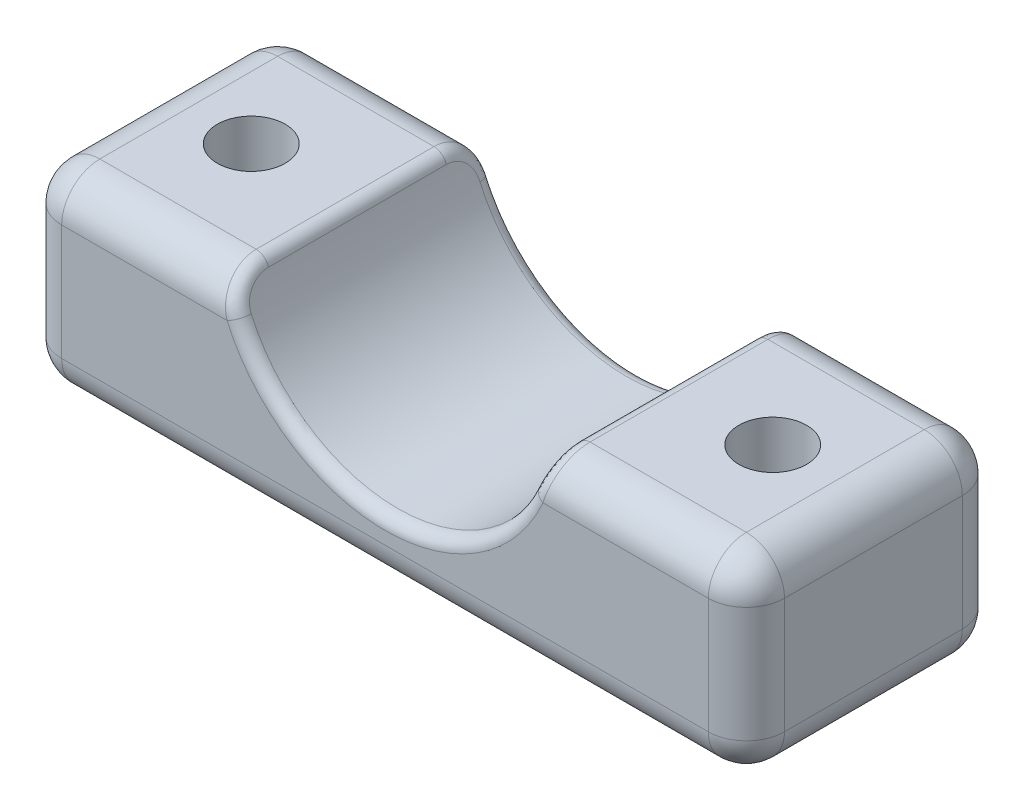
SolidWorks part; units mm, degrees
material "PLA ABS"
ref_plane "Front Plane" through (0, 0, 0) normal (0, 0, 1) x (1, 0, 0)
ref_plane "Top Plane" through (0, 0, 0) normal (0, 1, 0) x (1, 0, 0)
ref_plane "Right Plane" through (0, 0, 0) normal (1, 0, 0) x (0, 0, -1)
sketch "Sketch1" plane through (0, 0, 0) normal (0, 0, 1) x (1, 0, 0)
  line L0 (16.002, 22.352) -> (36.1315, 22.352)
  line L1 (-36.1315, 0) -> (36.1315, 0)
  line L2 (-36.1315, 0) -> (-36.1315, 22.352)
  line L3 (-36.1315, 22.352) -> (-16.002, 22.352)
  line L4 (36.1315, 0) -> (36.1315, 22.352)
  arc A0 (-16.002, 22.352) -> (16.002, 22.352) centre (0, 22.352) ccw
  dimension "D1" = 32.004
  dimension "D2" = 72.263
  dimension "D3" = 6.35
extrude "Boss-Extrude1" add sketch "Sketch1" along normal mid plane 25.4
sketch "Sketch2" plane through (0, 22.352, 0) normal (0, 1, 0) x (1, 0, 0)
  line L0 (-26.0668, 12.7) -> (-26.0667, -12.7) construction
  line L1 (-16.002, 12.7) -> (-36.1315, 12.7) construction
  line L2 (-16.002, -12.7) -> (-36.1315, -12.7) construction
  line L3 (0, 0) -> (0, 12.7) construction
  line L4 (16.002, 12.7) -> (-16.002, 12.7) construction
  circle A0 centre (-26.0668, 0) radius 3.3909
  circle A1 centre (26.0668, 0) radius 3.3909
  dimension "D1" = 6.7818
extrude "Cut-Extrude1" cut sketch "Sketch2" against normal through all
sketch "Sketch3" plane through (0, 0, 12.7) normal (0, 0, 1) x (1, 0, 0)
  line L0 (-16.002, 22.352) -> (-36.1315, 22.352) construction
  line L1 (-36.1315, 26.3528) -> (36.1315, 26.3528)
  line L2 (-36.1315, 26.3528) -> (-36.1315, 19.177)
  line L3 (-36.1315, 19.177) -> (36.1315, 19.177)
  line L4 (36.1315, 26.3528) -> (36.1315, 19.177)
  line L5 (-36.1315, 22.352) -> (-36.1315, 0) construction
  line L6 (36.1315, 0) -> (36.1315, 22.352) construction
  dimension "D1" = 3.175
extrude "Cut-Extrude2" cut sketch "Sketch3" against normal through all
sketch "Sketch6" plane through (0, 0, 0) normal (0, -1, 0) x (1, 0, 0)
  circle A0 centre (-26.0668, 0) radius 5.715
  circle A1 centre (26.0668, 0) radius 5.715
  dimension "D1" = 11.43
extrude "Cut-Extrude3" cut sketch "Sketch6" against normal blind 4.0716
fillet "Fillet3" radius 3.81 14 edges at (-36.1315, 0, 0) (-36.1315, 9.5885, -12.7) (-36.1315, 19.177, 0) (-36.1315, 9.5885, 12.7) (36.1315, 0, 0) (36.1315, 9.5885, 12.7) (36.1315, 19.177, 0) (36.1315, 9.5885, -12.7) (-25.9077, 19.177, 12.7) (25.9077, 19.177, 12.7) (0, 0, 12.7) (0, 0, -12.7) (25.9077, 19.177, -12.7) (-25.9077, 19.177, -12.7)
fillet "Fillet4" radius 1.27 8 edges at (15.3443, 17.8116, 11.8123) (15.6839, 19.177, 0) (15.5012, 18.3799, -11.2221) (0, 6.35, -12.7) (-15.3443, 17.8116, -11.8123) (-15.6839, 19.177, 0) (-15.5012, 18.3799, 11.2221) (0, 6.35, 12.7)
